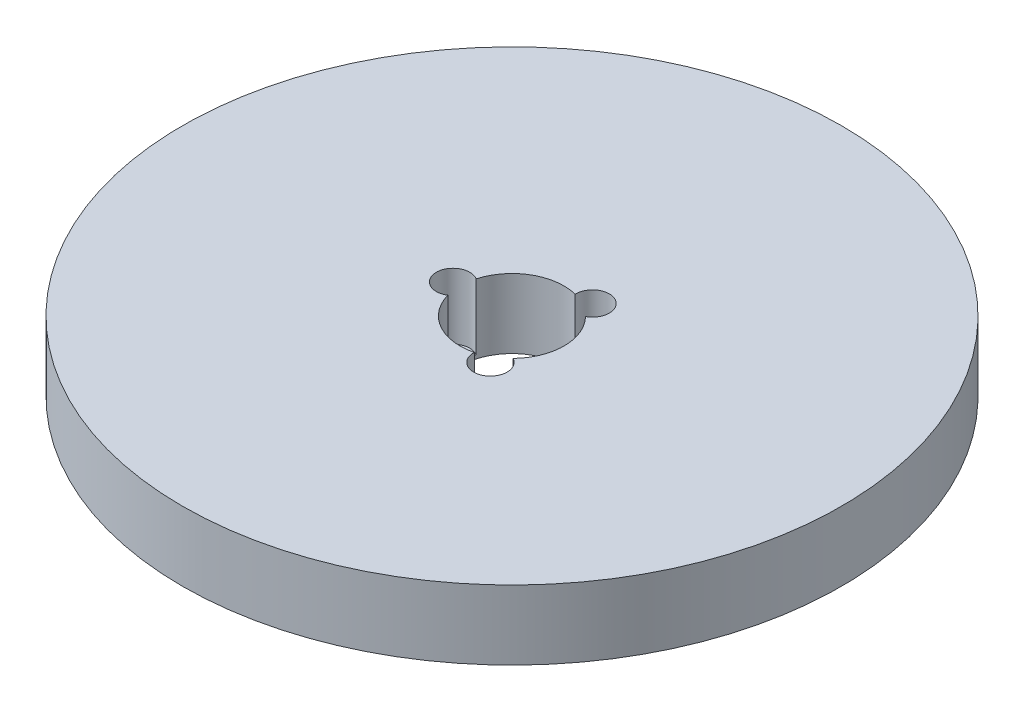
SolidWorks part; units mm, degrees
ref_plane "Front Plane" through (0, 0, 0) normal (0, 0, 1) x (1, 0, 0)
ref_plane "Top Plane" through (0, 0, 0) normal (0, 1, 0) x (1, 0, 0)
ref_plane "Right Plane" through (0, 0, 0) normal (1, 0, 0) x (0, 0, -1)
sketch "Sketch1" plane through (0, 0, 0) normal (0, 1, 0) x (1, 0, 0)
  circle A0 centre (0, 0) radius 47.5
  dimension "FLANGE_OD" = 95
extrude "Boss-Extrude1" add sketch "Sketch1" along normal blind 10
sketch "Sketch2" plane through (0, 0, 0) normal (0, 1, 0) x (1, 0, 0)
  circle A0 centre (0, 0) radius 7.5
  dimension "BORE_D" = 15
extrude "Cut-Extrude1" cut sketch "Sketch2" along normal through all
sketch "Sketch3" plane through (0, 10, 0) normal (0, 1, 0) x (1, 0, 0)
  circle A0 centre (0, 0) radius 8.4987 construction
  circle A1 centre (-8.4987, 0) radius 2.413
  dimension "BOLT_D" = 4.826
  dimension "BOLT_PCD" = 16.9975
extrude "Cut-Extrude2" cut sketch "Sketch3" against normal blind 9.4838
pattern_circular "CirPattern1" count 3 over 360 about axis through (0, 0, 0) along (0, 1, 0) of "Cut-Extrude2"
